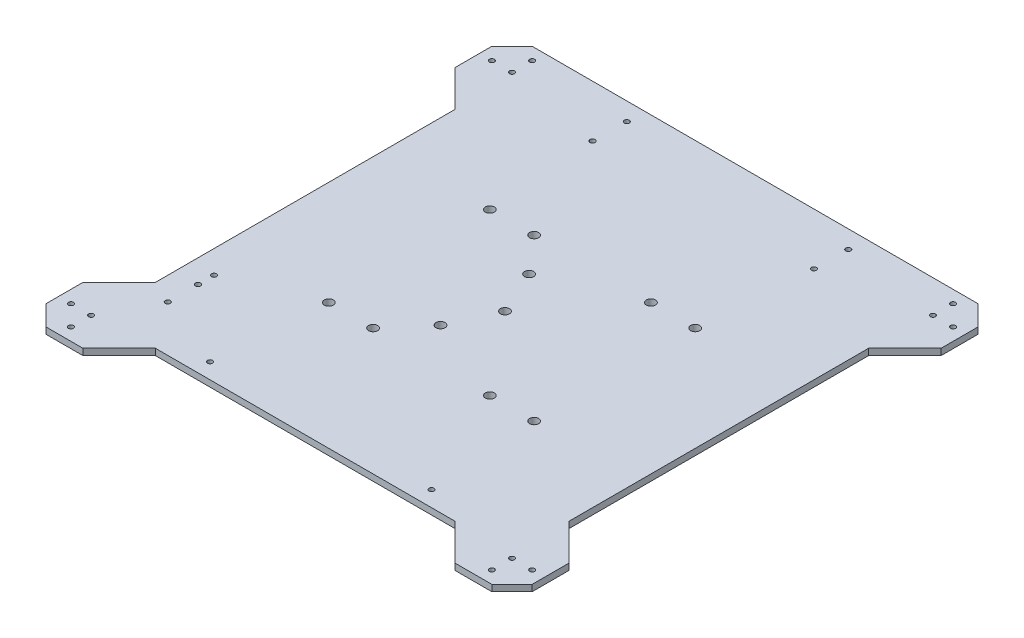
SolidWorks part; units mm, degrees
material "6061-T6 (SS)"
ref_plane "Front Plane" through (0, 0, 0) normal (0, 0, 1) x (1, 0, 0)
ref_plane "Top Plane" through (0, 0, 0) normal (0, 1, 0) x (1, 0, 0)
ref_plane "Right Plane" through (0, 0, 0) normal (1, 0, 0) x (0, 0, -1)
sketch "Sketch1" plane through (0, 0, 0) normal (0, 1, 0) x (1, 0, 0)
  line L0 (-120.75, 120.75) -> (120.75, -120.75) construction
  line L1 (-110.75, 120.75) -> (110.75, 120.75)
  line L2 (-120.75, 110.75) -> (-120.75, -110.75)
  line L3 (-110.75, -120.75) -> (110.75, -120.75)
  line L4 (120.75, 110.75) -> (120.75, -110.75)
  line L5 (110.75, -120.75) -> (120.75, -110.75)
  line L6 (110.75, 120.75) -> (120.75, 110.75)
  line L7 (-120.75, 110.75) -> (-110.75, 120.75)
  line L8 (-120.75, -110.75) -> (-110.75, -120.75)
  point P2 (-120.75, -120.75)
  point P3 (120.75, 120.75)
  dimension "D1" = 241.5
  dimension "D2" = 241.5
extrude "Boss-Extrude1" add sketch "Sketch1" along normal blind 3.175
sketch "Sketch2" plane through (0, 3.175, 0) normal (0, 1, 0) x (1, 0, 0)
  circle A0 centre (-51, -40) radius 1.5
  circle A2 centre (-29, -40) radius 2.25
  circle A5 centre (-51, 40) radius 1.5
  circle A6 centre (-29, 40) radius 2.25
  circle A9 centre (29, 40) radius 2.25
  circle A10 centre (51, 40) radius 2.25
  circle A14 centre (29, -40) radius 2.25
  circle A15 centre (51, -40) radius 2.25
  circle A16 centre (-3.5, 0) radius 2.25
  circle A17 centre (-13.5, 22) radius 2.25
  circle A18 centre (-13.5, -22) radius 2.25
  dimension "D1" = 3
  dimension "D2" = 4.5
extrude "Cut-Extrude1" cut sketch "Sketch2" against normal through all
hole_wizard "M3x0.5 Tapped Hole1" positions "Sketch4" profile "Sketch3" tap size "M3x0.5" standard "Ansi Metric" end condition through all
sketch "Sketch4" plane through (0, 3.175, 0) normal (0, 1, 0) x (-1, 0, 0)
  line L0 (110.75, 120.75) -> (-110.75, 120.75) construction
  line L1 (120.75, -110.75) -> (120.75, 110.75) construction
  line L2 (-110.75, -120.75) -> (110.75, -120.75) construction
  line L3 (-120.75, 110.75) -> (-120.75, -110.75) construction
  point P0 (114.55, -104.55)
  point P1 (104.55, -114.55)
  point P3 (-104.55, -114.55)
  point P5 (-114.55, -104.55)
  point P7 (-114.55, 104.55)
  point P9 (-104.55, 114.55)
  point P11 (104.55, 114.55)
  point P13 (114.55, 104.55)
  point P32 (-104.55, 104.55)
  point P34 (-104.55, -104.55)
  point P36 (104.55, -104.55)
  point P38 (104.55, 104.55)
  dimension "D1" = 16.2
  dimension "D2" = 6.2
  dimension "D3" = 6.2
  dimension "D4" = 16.2
  dimension "D5" = 16.2
  dimension "D6" = 6.2
  dimension "D7" = 6.2
  dimension "D8" = 16.2
sketch "Sketch3" plane through (-114.55, 3.175, -104.55) normal (1, 0, 0) x (0, 0, 1)
  line L0 (0, 0) -> (0, 3.175)
  line L1 (0, 3.175) -> (1.25, 3.175)
  line L2 (1.25, 3.175) -> (1.25, 0)
  line L5 (1.25, 0) -> (0, 0)
  line L11 (0, -6.35) -> (0, 107.95) construction
  dimension "Thru Tap Drill Dia." = 2.5
  dimension "Thru Tap Drill Depth" = 3.175
cosmetic thread "Hole Thread1" parameters "D2"=3
cosmetic thread "Hole Thread2" parameters "D2"=3
cosmetic thread "Hole Thread3" parameters "D2"=3
cosmetic thread "Hole Thread4" parameters "D2"=3
cosmetic thread "Hole Thread5" parameters "D2"=3
cosmetic thread "Hole Thread6" parameters "D2"=3
cosmetic thread "Hole Thread7" parameters "D2"=3
cosmetic thread "Hole Thread8" parameters "D2"=3
cosmetic thread "Hole Thread9" parameters "D2"=3
cosmetic thread "Hole Thread10" parameters "D2"=3
cosmetic thread "Hole Thread11" parameters "D2"=3
cosmetic thread "Hole Thread12" parameters "D2"=3
sketch "Sketch5" plane through (0, 3.175, 0) normal (0, 1, 0) x (1, 0, 0)
  circle A0 centre (-55, 95) radius 1.25
  circle A1 centre (55, 95) radius 1.25
  circle A2 centre (-55, -95) radius 1.25
  circle A3 centre (55, -95) radius 1.25
  dimension "D1" = 2.5
extrude "Cut-Extrude2" cut sketch "Sketch5" against normal through all
sketch "Sketch6" plane through (0, 3.175, 0) normal (0, 1, 0) x (1, 0, 0)
  line L0 (-110.75, -120.75) -> (110.75, -120.75) construction
  line L1 (-120.75, 110.75) -> (-120.75, -110.75) construction
  circle A0 centre (-91.25, -64.75) radius 1.25
  circle A1 centre (-91.25, -56.75) radius 1.25
  circle A2 centre (-91.25, -79.75) radius 1.25
  dimension "D3" = 2.5
  dimension "D1" = 56
  dimension "D2" = 29.5
  dimension "D4" = 8
  dimension "D5" = 15
extrude "Cut-Extrude3" cut sketch "Sketch6" against normal blind 10
hole_wizard "M4 Clearance Hole1" positions "Sketch8" profile "Sketch7" hole size "M4" standard "ANSI Metric"
sketch "Sketch8" plane through (0, 3.175, 0) normal (0, 1, 0) x (-1, 0, 0)
  point P0 (51, -40)
  point P1 (51, 40)
sketch "Sketch7" plane through (-51, 3.175, -40) normal (1, 0, 0) x (0, 0, 1)
  line L0 (0, 0) -> (0, 11.3519)
  line L1 (0, 11.3519) -> (2.25, 10)
  line L2 (2.25, 10) -> (2.25, 0)
  line L5 (2.25, 0) -> (0, 0)
  line L10 (0, 11.3519) -> (-2.25, 10) construction
  line L11 (0, -6.35) -> (0, 107.95) construction
  dimension "Hole Dia." = 4.5
  dimension "Hole Depth" = 10
  dimension "Drill Angle" = 118
sketch "Sketch9" plane through (0, 3.175, 0) normal (0, 1, 0) x (1, 0, 0)
  line L0 (-120.75, 92.4657) -> (-102.75, 74.4657)
  line L1 (-120.75, 110.75) -> (-120.75, -110.75) construction
  line L2 (-102.75, 74.4657) -> (-102.75, -74.4657)
  line L3 (-102.75, -74.4657) -> (-120.75, -92.4657)
  line L4 (-120.75, 92.4657) -> (-120.75, -92.4657)
  line L5 (120.75, 92.4657) -> (102.75, 74.4657)
  line L6 (120.75, -110.75) -> (120.75, 110.75) construction
  line L7 (102.75, 74.4657) -> (102.75, -74.4657)
  line L8 (102.75, -74.4657) -> (120.75, -92.4657)
  line L9 (120.75, -92.4657) -> (120.75, 92.4657)
  line L10 (-92.4657, -120.75) -> (-74.4657, -102.75)
  line L11 (-110.75, -120.75) -> (110.75, -120.75) construction
  line L12 (-74.4657, -102.75) -> (74.4657, -102.75)
  line L13 (74.4657, -102.75) -> (92.4657, -120.75)
  line L14 (92.4657, -120.75) -> (-92.4657, -120.75)
  line L16 (110.75, 120.75) -> (-110.75, 120.75) construction
  circle A0 centre (-104.55, -104.55) radius 1.25 construction
  circle A1 centre (104.55, -104.55) radius 1.25 construction
  circle A2 centre (104.55, 104.55) radius 1.25 construction
  circle A3 centre (-104.55, 104.55) radius 1.25 construction
  dimension "D6" = 20
  dimension "D1" = 45
  dimension "D2" = 18
  dimension "D3" = 18
  dimension "D4" = 18
  dimension "D5" = 20
  dimension "D7" = 20
  dimension "D8" = 20
  dimension "D9" = 20
  dimension "D10" = 20
extrude "Cut-Extrude4" cut sketch "Sketch9" against normal blind 10
hole_wizard "M3x0.5 Tapped Hole2" positions "Sketch14" profile "Sketch13" tap size "M3x0.5" standard "ANSI Metric" end condition through all
sketch "Sketch14" plane through (0, 3.175, 0) normal (0, 1, 0) x (-1, 0, 0)
  point P0 (-55.1885, -111.8444)
  point P2 (54.8115, -111.8444)
  dimension "D1" = 110
sketch "Sketch13" plane through (55.1885, 3.175, -111.8444) normal (1, 0, 0) x (0, 0, 1)
  line L0 (0, 0) -> (0, 3.175)
  line L1 (0, 3.175) -> (1.25, 3.175)
  line L2 (1.25, 3.175) -> (1.25, 0)
  line L5 (1.25, 0) -> (0, 0)
  line L11 (0, -6.35) -> (0, 107.95) construction
  dimension "Thru Tap Drill Dia." = 2.5
  dimension "Thru Tap Drill Depth" = 3.175
cosmetic thread "Hole Thread13" parameters "D2"=3
cosmetic thread "Hole Thread14" parameters "D2"=3
